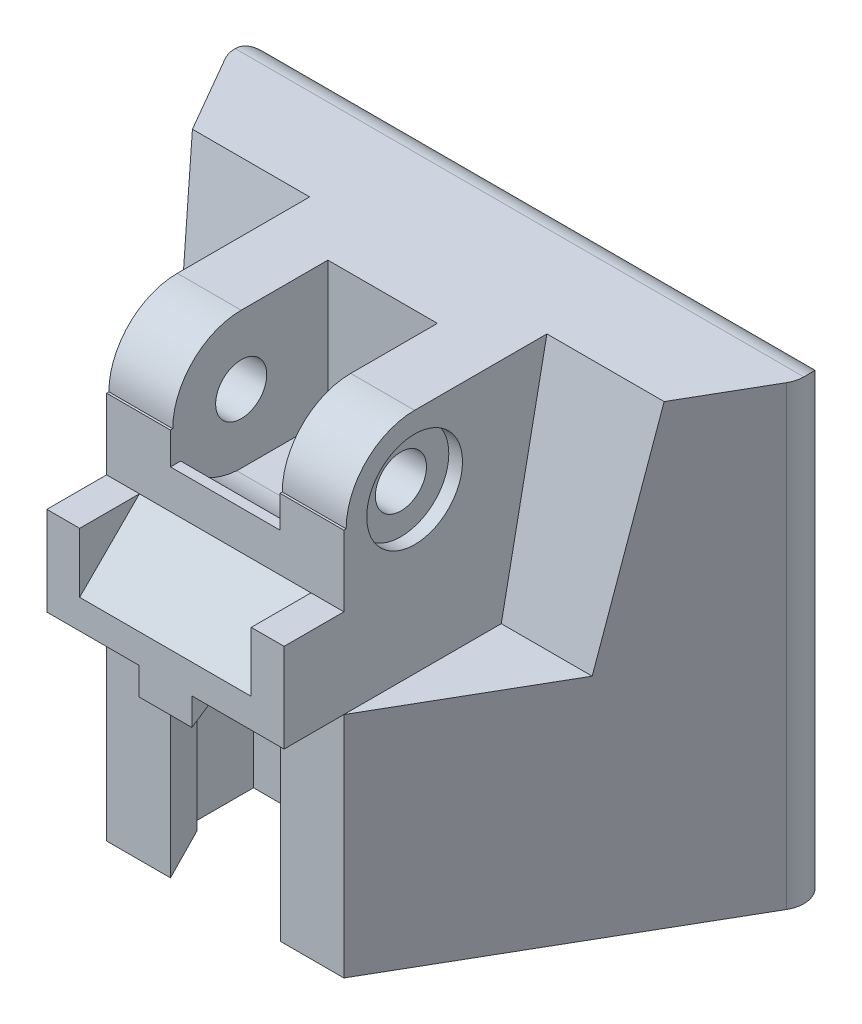
SolidWorks part; units mm, degrees
material "Plastique personnalisé"
ref_plane "前视基准面" through (0, 0, 0) normal (0, 0, 1) x (1, 0, 0)
ref_plane "上视基准面" through (0, 0, 0) normal (0, 1, 0) x (1, 0, 0)
ref_plane "右视基准面" through (0, 0, 0) normal (1, 0, 0) x (0, 0, -1)
sketch "Sketch1" plane through (0, 0, 0) normal (0, 1, 0) x (1, 0, 0)
  line L1 (-13, 14) -> (13, 14)
  line L2 (-13, 14) -> (-13, -14)
  line L3 (-13, -14) -> (13, -14)
  line L4 (13, 14) -> (13, -14)
  line L5 (-13, 14) -> (13, -14) construction
  line L6 (-13, -14) -> (13, 14) construction
  point P0 (0, 0)
  dimension "D1" = 26
  dimension "D2" = 28
extrude "Boss-Extrude1" add sketch "Sketch1" along normal blind 50
sketch "Sketch3" plane through (0, 0, 0) normal (0, 1, 0) x (1, 0, 0)
  line L0 (9.999, 2.65) -> (9.999, 9.85)
  line L1 (9.999, 9.85) -> (2.9003, 9.85)
  line L2 (-10, 9.85) -> (-10, 2.65)
  line L3 (-2.9, 9.85) -> (-10, 9.85)
  line L4 (-10, -3.25) -> (-10, -4.35)
  line L5 (6.0729, -3.25) -> (10.0625, -3.25)
  line L7 (13, 14) -> (-13, 14) construction
  line L8 (10.19, -15.102) -> (-10, -15.0895)
  line L9 (2.9003, 9.85) -> (2.8812, 5.8228)
  line L10 (13, -14) -> (13, 14) construction
  line L11 (-10, -3.25) -> (-6, -3.25)
  line L12 (2.8812, 5.8228) -> (-2.9188, 5.85)
  line L14 (-10, 2.65) -> (-9, 2.65)
  line L15 (9.999, 2.65) -> (8.999, 2.65)
  line L16 (-6, -3.25) -> (-9, 2.65)
  line L17 (6.0729, -3.25) -> (8.999, 2.65)
  line L22 (-10, -3.25) -> (-6, -3.25)
  line L31 (10.1233, -8.8993) -> (10.19, -15.102)
  line L38 (-2.9, 9.85) -> (-2.9188, 5.85)
  line L47 (-10, -4.35) -> (-10, -15.0895)
  line L53 (10.0689, -3.8496) -> (10.0625, -3.2497)
  line L55 (10.1233, -8.8993) -> (10.0689, -3.8496)
  point P38 (10, 3.3)
  point P94 (-3.25, -9.8)
  point P121 (3.25, -9.8)
  dimension "D3" = 7.1
  dimension "D4" = 5.8
  dimension "D5" = 0
  dimension "D6" = 5.9
  dimension "D2" = 1
  dimension "D8" = 5.9
  dimension "D9" = 7.2
  dimension "D10" = 7.2
  dimension "D12" = 4.15
extrude "Cut-Extrude6" cut sketch "Sketch3" along normal blind 25 contours L9 L1 L55 L31 L8 L47 L22 region at (0.038, 0, 3.3058)
sketch "Sketch7" plane through (13, 0, 0) normal (1, 0, 0) x (0, 0, -1)
  line L0 (4.5, 50) -> (-14, 50)
  line L1 (-14, 50) -> (-14, 24)
  line L2 (-14, 50) -> (-14, 0) construction
  line L3 (-14, 24) -> (-0.8033, 37.1967)
  line L4 (7.5, 35.3637) -> (14, 50) construction
  line L6 (14, 50) -> (14, 0) construction
  line L7 (14, 42.5) -> (4.5, 42.5) construction
  arc A0 (-0.8033, 37.1967) -> (4.5, 50) centre (4.5, 42.5) ccw
  dimension "D2" = 7.5
  dimension "D5" = 15
  dimension "D1" = 26
  dimension "D3" = 9.5
  dimension "D4" = 45
extrude "Cut-Extrude3" cut sketch "Sketch7" against normal blind 39
sketch "Sketch14" plane through (13, 0, 0) normal (1, 0, 0) x (0, 0, -1)
  line L0 (14, 50) -> (14, 0) construction
  circle A0 centre (4.5, 42.5) radius 7.5
  dimension "D1" = 9.5
extrude "Boss-Extrude7" add sketch "Sketch14" against normal blind 7
mirror "Symétrie1" about plane through (0, 0, 0) normal (1, 0, 0) of "Boss-Extrude7"
sketch "Sketch15" plane through (13, 0, 0) normal (1, 0, 0) x (0, 0, -1)
  line L0 (14, 50) -> (14, 0) construction
  line L1 (4.5, 42.5) -> (1.6109, 40.6109) construction
  line L2 (4.5, 50) -> (14, 50) construction
  circle A1 centre (4.5, 42.5) radius 2.8
  dimension "D1" = 5.6
  dimension "D2" = 9.5
  dimension "D3" = 7.5
extrude "Cut-Extrude4" cut sketch "Sketch15" against normal blind 28
sketch "Sketch16" plane through (13, 0, 0) normal (1, 0, 0) x (0, 0, -1)
  circle A0 centre (4.5, 42.5) radius 5.25
  dimension "D1" = 10.5
extrude "Cut-Extrude5" cut sketch "Sketch16" against normal blind 1.5
mirror "Mirror3" about plane through (0, 0, 0) normal (1, 0, 0) of "Cut-Extrude5"
sketch "Sketch17" plane through (0, 0, 0) normal (0, -1, 0) x (1, 0, 0)
  line L0 (-9.3, 3.25) -> (-13, 3.25)
  line L2 (9.3, 3.25) -> (9.3, 9.8)
  line L3 (-13, -14) -> (-13, 14) construction
  line L4 (-13, 3.25) -> (-13, 14)
  line L5 (-9.3, 3.25) -> (-9.3, 9.8)
  line L6 (-13, 14) -> (13, 14)
  line L8 (13, 14) -> (13, 3.25)
  line L9 (13, 14) -> (13, -14) construction
  line L10 (13, 3.25) -> (9.3, 3.25)
  line L14 (9.3, 9.8) -> (-9.3, 9.8)
extrude "Cut-Extrude7" cut sketch "Sketch17" against normal through all
sketch "Sketch19" plane through (0, 0, -14) normal (0, 0, -1) x (-1, 0, 0)
  line L0 (-13, 0) -> (13, 0) construction
  circle A0 centre (0, 15) radius 2.15
  point P2 (0, 0)
  dimension "D1" = 4.3
  dimension "D2" = 15
extrude "Cut-Extrude9" cut sketch "Sketch19" against normal blind 50
sketch "Sketch20" plane through (0, 0, -14) normal (0, 0, -1) x (-1, 0, 0)
  circle A0 centre (0, 15) radius 4
  dimension "D1" = 8
extrude "Cut-Extrude10" [suppressed] cut sketch "Sketch20" against normal blind 3
sketch "Esquisse1" plane through (0, 50, 0) normal (0, 1, 0) x (1, 0, 0)
  line L0 (13, 14) -> (-13, 14) construction
  line L1 (6, 4.5) -> (-6, 4.5)
  line L2 (6, 4.5) -> (6, 14)
  line L3 (6, 14) -> (-6, 14)
  line L4 (-6, 4.5) -> (-6, 14)
  dimension "D1" = 12
extrude "Enlèv. mat.-Extru.1" cut sketch "Esquisse1" against normal blind 7.5
sketch "Esquisse2" plane through (-13, 0, 0) normal (-1, 0, 0) x (0, 0, 1)
  line L0 (3.25, 0) -> (-14, 0) construction
  line L3 (-14, 50) -> (-14, 0) construction
  circle A0 centre (-8, 14.2) radius 1.7
  circle A1 centre (-3, 5.2) radius 1.7
  dimension "D5" = 3.4
  dimension "D6" = 3.4
  dimension "D1" = 5.2
  dimension "D2" = 14.2
  dimension "D3" = 6
  dimension "D4" = 11
extrude "Enlèv. mat.-Extru.2" [suppressed] cut sketch "Esquisse2" against normal blind 7.5
mirror "Symétrie2" [suppressed] about plane through (0, 0, 0) normal (1, 0, 0)
sketch "Esquisse3" plane through (0, 0, -14) normal (0, 0, -1) x (-1, 0, 0)
  line L1 (6, 42.5) -> (-6, 42.5)
  line L2 (6, 42.5) -> (6, 35)
  line L3 (6, 35) -> (-6, 35)
  line L4 (-6, 42.5) -> (-6, 35)
  dimension "D1" = 12
  dimension "D2" = 7.5
extrude "Enlèv. mat.-Extru.3" cut sketch "Esquisse3" against normal blind 10
sketch "Esquisse5" plane through (13, 0, 0) normal (1, 0, 0) x (0, 0, -1)
  line L1 (-3.25, 42.5) -> (-3, 42.5)
  arc A0 (4.5, 50) -> (-0.8033, 37.1967) centre (4.5, 42.5) ccw construction
chamfer "Chanfrein1" [suppressed] distance 1 angle 45
chamfer "Chanfrein2" [suppressed] distance 1 angle 45
sketch "Esquisse6" plane through (13, 0, 0) normal (1, 0, 0) x (0, 0, -1)
  line L0 (-3.25, 34.75) -> (-3.25, 42.5)
  line L1 (-3.25, 42.5) -> (-3, 42.5)
  line L2 (-3.25, 34.75) -> (-0.8033, 37.1967)
  arc A0 (-3, 42.5) -> (-0.8033, 37.1967) centre (4.5, 42.5) ccw
extrude "Boss.-Extru.1" add sketch "Esquisse6" against normal blind 26
sketch "Sketch18" plane through (0, 0, 0) normal (1, 0, 0) x (0, 0, -1)
  line L0 (-2.0267, 35.9733) -> (-2.0267, 31.9733)
  line L2 (-2.0267, 31.9733) -> (-6.0267, 31.9733)
  line L3 (-3.25, 34.75) -> (-6.0267, 31.9733)
  line L4 (-2.0267, 35.9733) -> (-3.25, 35.9733)
  line L6 (-3.25, 34.75) -> (-3.25, 35.9733)
  line L7 (-3.25, 42.5) -> (-3.25, 0) construction
  dimension "D1" = 4
  dimension "D2" = 4
extrude "Enlèv. mat.-Extru.4" [suppressed] cut sketch "Sketch18" against normal blind 3.45 and the other way blind 3.45
sketch "Esquisse7" plane through (0, 42.5, 0) normal (0, 1, 0) x (1, 0, 0)
  line L0 (6, -3) -> (6, -7.0964)
  line L1 (6, -7.0964) -> (-6, -3.7801)
  line L2 (-6, -3.7801) -> (-6, 8.4569)
  line L3 (-6, 8.4569) -> (6, -3)
extrude "Enlèv. mat.-Extru.5" cut sketch "Esquisse7" against normal blind 3.5
sketch "Esquisse8" plane through (0, 42.5, 0) normal (0, 1, 0) x (1, 0, 0)
sketch "Esquisse9" plane through (0, 25, 0) normal (0, -1, 0) x (-1, 0, 0)
  line L0 (9.3, -9.8) -> (-9.3, -9.8) construction
  line L1 (2.9, -9.8) -> (-2.9, -9.8)
  line L2 (2.9, -9.8) -> (2.9, -6.8)
  line L3 (2.9, -6.8) -> (-2.9, -6.8)
  line L4 (-2.9, -9.8) -> (-2.9, -6.8)
  line L5 (9.3, -3.25) -> (9.3, -9.8) construction
  dimension "D1" = 5.8
  dimension "D2" = 3
  dimension "D3" = 6.4
extrude "Boss.-Extru.3" add sketch "Esquisse9" along normal blind 1
sketch "Esquisse10" plane through (-2.9, 0, 0) normal (-1, 0, 0) x (0, 0, 1)
  line L0 (9.8, 24) -> (9.8, 22)
  line L1 (9.8, 22) -> (6.8, 24)
  line L2 (9.8, 24) -> (6.8, 24)
  dimension "D1" = 2
extrude "Boss.-Extru.4" add sketch "Esquisse10" against normal up to vertex (5.8 mm away) up to point (2.9, 24, 6.8)
sketch "Esquisse11" plane through (-9.3, 0, 0) normal (-1, 0, 0) x (0, 0, 1)
  line L0 (3.25, 34.75) -> (9.8, 28.2)
  line L2 (3.25, 34.75) -> (3.25, 25)
  line L3 (3.25, 25) -> (9.8, 25)
  line L4 (9.8, 28.2) -> (9.8, 25)
extrude "Boss.-Extru.5" add sketch "Esquisse11" along normal blind 0.1
sketch "Esquisse12" plane through (9.3, 0, 0) normal (1, 0, 0) x (0, 0, -1)
  line L0 (-9.8, 25) -> (-9.8, 28.2)
  line L1 (-9.8, 28.2) -> (-3.25, 34.75)
  line L2 (-3.25, 34.75) -> (-3.25, 25)
  line L3 (-3.25, 25) -> (-9.8, 25)
extrude "Boss.-Extru.6" add sketch "Esquisse12" along normal blind 0.1
sketch "Esquisse13" plane through (9.4, 0, 0) normal (1, 0, 0) x (0, 0, -1)
  line L1 (-3.25, 34.75) -> (-9.8, 34.75)
  line L2 (-3.25, 34.75) -> (-3.25, 25)
  line L3 (-3.25, 25) -> (-9.8, 25)
  line L4 (-9.8, 34.75) -> (-9.8, 25)
extrude "Boss.-Extru.7" add sketch "Esquisse13" along normal up to vertex (3.6 mm away) up to point (13, 42.5, 3.25)
sketch "Esquisse14" plane through (-9.4, 0, 0) normal (-1, 0, 0) x (0, 0, 1)
  line L1 (3.25, 34.75) -> (9.8, 34.75)
  line L2 (3.25, 34.75) -> (3.25, 25)
  line L3 (3.25, 25) -> (9.8, 25)
  line L4 (9.8, 34.75) -> (9.8, 25)
extrude "Boss.-Extru.8" add sketch "Esquisse14" along normal up to vertex (3.6 mm away) up to point (-13, 42.5, 3.25)
sketch "Esquisse16" plane through (-13, 0, 0) normal (-1, 0, 0) x (0, 0, 1)
  line L0 (3.25, 0) -> (-14, 0)
  line L1 (-14, 0) -> (-14, 50)
  line L2 (-14, 50) -> (-4.5, 50)
  line L4 (3, 42.5) -> (3.25, 42.5)
  line L5 (3.25, 42.5) -> (3.25, 34.75)
  line L6 (3.25, 34.75) -> (9.8, 34.75)
  line L7 (9.8, 34.75) -> (9.8, 25)
  line L8 (9.8, 25) -> (3.25, 25)
  line L9 (3.25, 25) -> (3.25, 0)
  circle A0 centre (-4.5, 42.5) radius 5.25
  arc A1 (-4.5, 50) -> (3, 42.5) centre (-4.5, 42.5) cw
extrude "Boss.-Extru.9" [suppressed] add sketch "Esquisse16" along normal blind 1
sketch "Esquisse17" plane through (13, 0, 0) normal (1, 0, 0) x (0, 0, -1)
  line L0 (-3, 42.5) -> (-3.25, 42.5)
  line L1 (-3.25, 42.5) -> (-3.25, 34.75)
  line L2 (-3.25, 34.75) -> (-9.8, 34.75)
  line L3 (-9.8, 34.75) -> (-9.8, 25)
  line L4 (-9.8, 25) -> (-3.25, 25)
  line L5 (-3.25, 25) -> (-3.25, 0)
  line L6 (-3.25, 0) -> (14, 0)
  line L7 (14, 0) -> (14, 50)
  line L8 (14, 50) -> (4.5, 50)
  arc A0 (4.5, 50) -> (-3, 42.5) centre (4.5, 42.5) ccw
  circle A1 centre (4.5, 42.5) radius 5.25
extrude "Boss.-Extru.10" [suppressed] add sketch "Esquisse17" along normal blind 1
sketch "Esquisse18" plane through (0, 0, 0) normal (0, -1, 0) x (1, 0, 0)
  line L0 (-13, 3.25) -> (-33.3516, -32)
  line L1 (-13, 3.25) -> (-6, 3.25) construction
  line L2 (-13, -14) -> (-13, 3.25) construction
  line L3 (-33.3516, -32) -> (33.3516, -32)
  line L4 (33.3516, -32) -> (13, 3.25)
  line L5 (13, -14) -> (-13, -14) construction
  line L6 (-13, 3.25) -> (-13, -14)
  line L7 (-13, -14) -> (13, -14)
  line L8 (13, -14) -> (13, 3.25)
  dimension "D1" = 60
  dimension "D2" = 60
  dimension "D3" = 18
extrude "Boss.-Extru.11" add sketch "Esquisse18" against normal up to vertex (25 mm away) up to point (-13, 25, 9.8)
sketch "Esquisse19" plane through (0, 25, 0) normal (0, 1, 0) x (1, 0, 0)
  line L0 (33.3516, 32) -> (22.9593, 14)
  line L2 (-22.9593, 14) -> (22.9593, 14)
  line L3 (-33.3516, 32) -> (-22.9593, 14)
  line L5 (33.3516, 32) -> (-33.3516, 32)
extrude "Boss.-Extru.12" add sketch "Esquisse19" along normal up to vertex (25 mm away) up to point (6, 50, -14)
sketch "Esquisse20" plane through (13, 0, 0) normal (1, 0, 0) x (0, 0, -1)
  line L0 (14, 25) -> (14, 50)
  line L1 (14, 50) -> (19, 50)
  line L2 (19, 50) -> (14, 25)
  dimension "D1" = 5
extrude "Enlèv. mat.-Extru.6" cut sketch "Esquisse20" along normal blind 28
mirror "Symétrie3" about plane through (0, 0, 0) normal (1, 0, 0) of "Enlèv. mat.-Extru.6"
fillet "Congé1" radius 3 3 edges at (-33.3516, 25, -32) (0, 50, -32) (33.3516, 25, -32)
